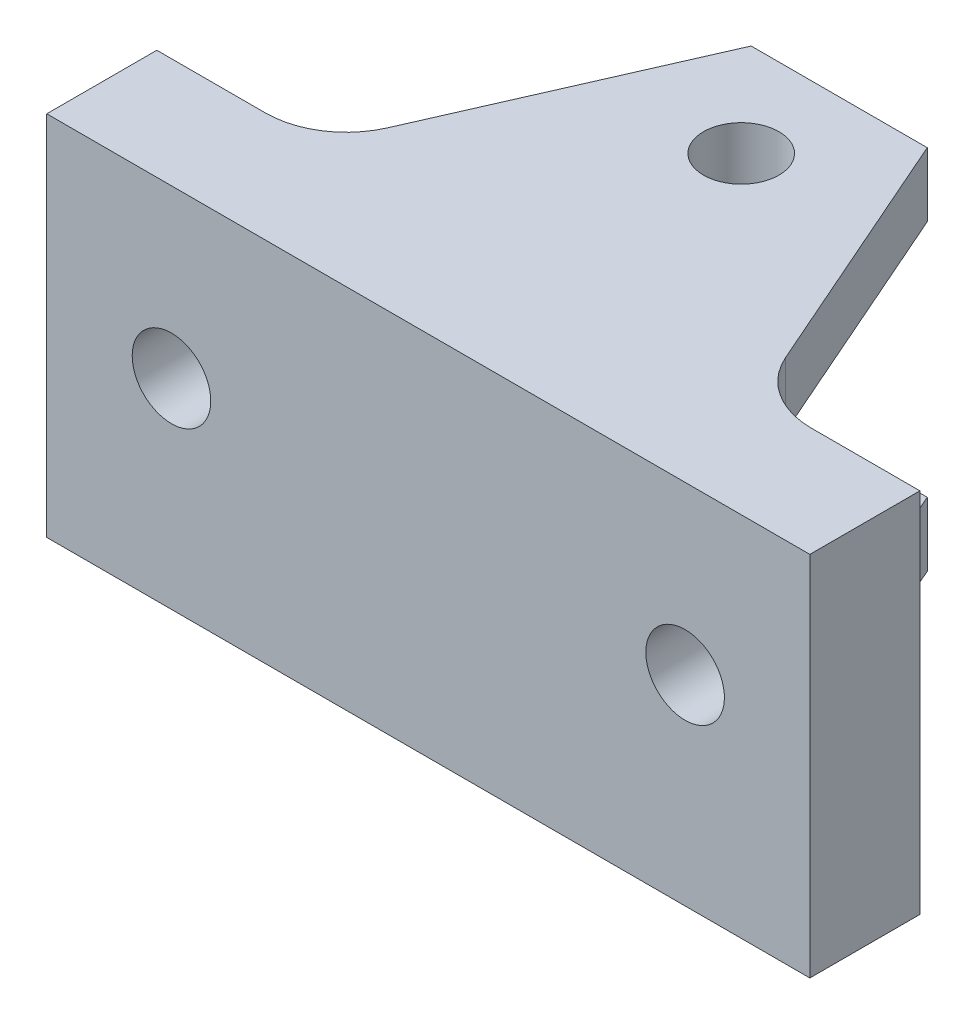
SolidWorks part; units mm, degrees
material "Custom Plastic"
ref_plane "X-Y Datum" through (0, 0, 0) normal (0, 0, 1) x (1, 0, 0)
ref_plane "X-Z Datum" through (0, 0, 0) normal (0, 1, 0) x (1, 0, 0)
ref_plane "Y-Z Datum" through (0, 0, 0) normal (1, 0, 0) x (0, 0, -1)
sketch "Sketch1" plane through (0, 0, 0) normal (1, 0, 0) x (0, 0, -1)
  line L0 (0, 8.7126) -> (0, 40.4626)
  line L1 (0, 40.4626) -> (39.7797, 40.4626)
  line L2 (39.7797, 40.4626) -> (39.7797, 34.9127)
  line L3 (39.7797, 34.9127) -> (9.525, 34.9127)
  line L4 (9.525, 34.9127) -> (9.525, 14.2625)
  line L5 (9.525, 14.2625) -> (39.7797, 14.2625)
  line L6 (39.7797, 14.2625) -> (39.7797, 8.7126)
  line L7 (39.7797, 8.7126) -> (0, 8.7126)
  line L8 (29.6197, 40.4626) -> (29.6197, 8.7126) construction
  line L9 (0, 26.0299) -> (9.525, 26.0299) construction
  line L10 (0, 22.0299) -> (0, 30.0299) construction
  circle A0 centre (29.6197, 24.5876) radius 10.3251 construction
  dimension "D5" = 20.6502
  dimension "D1" = 20.6502
  dimension "D2" = 31.75
  dimension "D3" = 10.16
  dimension "D4" = 9.525
extrude "Boss-Extrude1" add sketch "Sketch1" along normal blind 76.2
sketch "Sketch2" plane through (0, 0, -9.525) normal (0, 0, -1) x (-1, 0, 0)
  line L0 (-38.1, 34.9127) -> (-38.1, 14.2625) construction
  line L1 (-76.2, 34.9127) -> (0, 34.9127) construction
  line L2 (-76.2, 14.2625) -> (0, 14.2625) construction
  line L3 (-60.325, 26.0299) -> (-15.875, 26.0299) construction
  circle A0 centre (-60.325, 26.0299) radius 3.4
  circle A1 centre (-15.875, 26.0299) radius 3.4
  point P8 (-38.1, 26.0299)
  dimension "D2" = 6.8
  dimension "D1" = 44.45
extrude "Cut-Extrude1" cut sketch "Sketch2" against normal up to surface (9.525 mm away) up to face at (38.1, 24.5876, 0)
sketch "Sketch3" plane through (0, 40.4626, 0) normal (0, 1, 0) x (1, 0, 0)
  line L0 (76.2, 39.7797) -> (0, 39.7797) construction
  line L1 (30.48, 35.56) -> (19.05, 9.525)
  line L2 (45.72, 35.56) -> (57.15, 9.525)
  line L3 (30.48, 35.56) -> (45.72, 35.56)
  line L4 (0, 39.7797) -> (0, 9.525)
  line L5 (0, 0) -> (0, 39.7797) construction
  line L6 (0, 9.525) -> (19.05, 9.525)
  line L7 (0, 39.7797) -> (76.2, 39.7797)
  line L8 (76.2, 39.7797) -> (76.2, 9.525)
  line L9 (76.2, 39.7797) -> (76.2, 0) construction
  line L10 (76.2, 9.525) -> (57.15, 9.525)
  line L12 (76.2, 0) -> (0, 0) construction
  circle A0 centre (38.1, 27.0797) radius 3.2639
  point P4 (38.1, 39.7797)
  dimension "D1" = 6.5278
  dimension "D2" = 12.7
  dimension "D3" = 15.24
  dimension "D4" = 35.56
  dimension "D5" = 19.05
extrude "Cut-Extrude2" cut sketch "Sketch3" against normal up to surface (31.75 mm away) up to face at (38.1, 8.7126, -19.8899)
sketch "Sketch4" plane through (0, 0, -9.525) normal (0, 0, -1) x (-1, 0, 0)
  line L0 (0, 40.4626) -> (-19.05, 40.4626) construction
  line L1 (0, 8.7126) -> (-5.08, 8.7126)
  line L2 (0, 8.7126) -> (0, 40.4626)
  line L3 (0, 40.4626) -> (-5.08, 40.4626)
  line L4 (-5.08, 8.7126) -> (-5.08, 40.4626)
  line L5 (-57.15, 40.4626) -> (-76.2, 40.4626) construction
  line L6 (-76.2, 8.7126) -> (-71.12, 8.7126)
  line L7 (-76.2, 8.7126) -> (-76.2, 40.4626)
  line L8 (-76.2, 40.4626) -> (-71.12, 40.4626)
  line L9 (-71.12, 8.7126) -> (-71.12, 40.4626)
  dimension "D1" = 5.08
extrude "Cut-Extrude3" cut sketch "Sketch4" against normal up to surface (9.525 mm away) up to face at (60.325, 29.4299, 0)
fillet "Fillet1" radius 6.985 4 edges at (57.15, 37.6877, -9.525) (57.15, 11.4876, -9.525) (19.05, 37.6877, -9.525) (19.05, 11.4876, -9.525)
